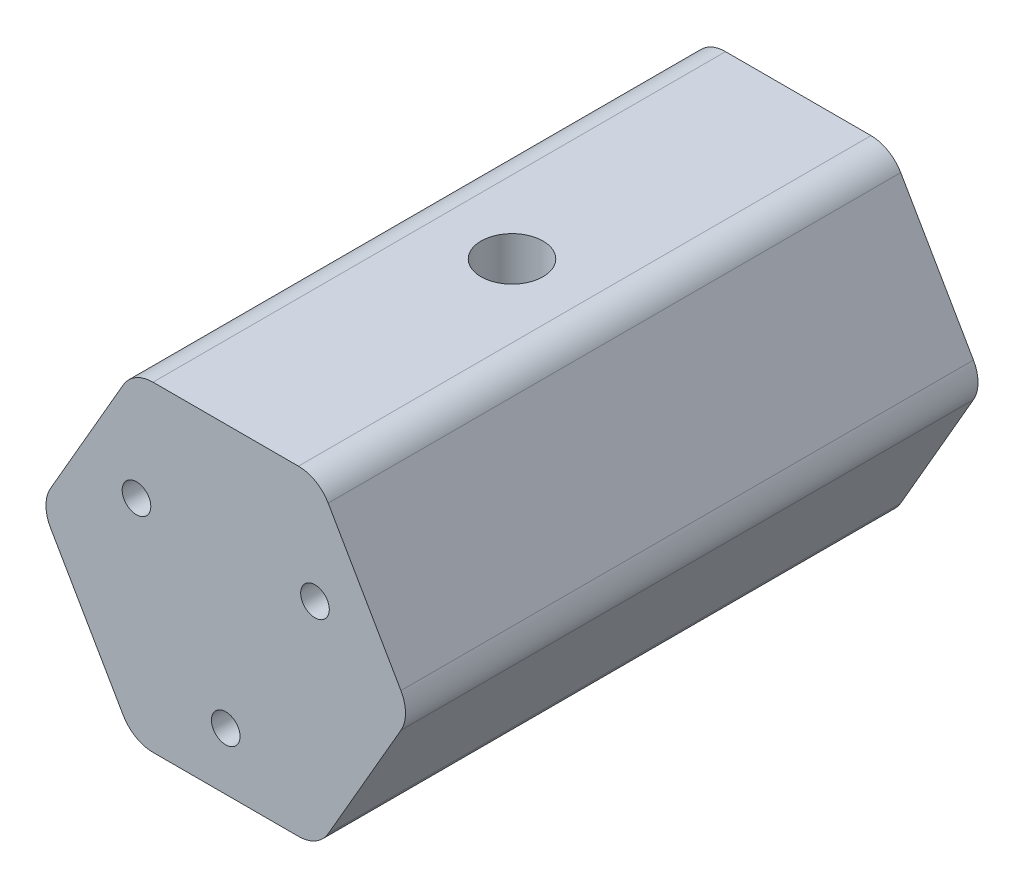
SolidWorks part; units mm, degrees
ref_plane "Front Plane" through (0, 0, 0) normal (0, 0, 1) x (1, 0, 0)
ref_plane "Top Plane" through (0, 0, 0) normal (0, 1, 0) x (1, 0, 0)
ref_plane "Right Plane" through (0, 0, 0) normal (1, 0, 0) x (0, 0, -1)
sketch "Sketch1" plane through (0, 0, 0) normal (0, 0, 1) x (1, 0, 0)
  line L7 (-6.3509, -14) -> (6.3509, -14)
  line L8 (8.9489, -12.5) -> (15.2998, -1.5)
  line L9 (15.2998, 1.5) -> (8.9489, 12.5)
  line L10 (6.3509, 14) -> (-6.3509, 14)
  line L11 (-8.9489, 12.5) -> (-15.2998, 1.5)
  line L12 (-15.2998, -1.5) -> (-8.9489, -12.5)
  circle A0 centre (0, 0) radius 9 construction
  circle A1 centre (-7.7942, 4.5) radius 1.25
  circle A2 centre (7.7942, 4.5) radius 1.25
  circle A3 centre (0, -9) radius 1.25
  circle A4 centre (0, 0) radius 14 construction
  arc A5 (-6.3509, -14) -> (-8.9489, -12.5) centre (-6.3509, -11) cw
  arc A6 (6.3509, -14) -> (8.9489, -12.5) centre (6.3509, -11) ccw
  arc A8 (15.2998, -1.5) -> (15.2998, 1.5) centre (12.7017, 0) ccw
  arc A9 (8.9489, 12.5) -> (6.3509, 14) centre (6.3509, 11) ccw
  arc A10 (-6.3509, 14) -> (-8.9489, 12.5) centre (-6.3509, 11) ccw
  arc A11 (-15.2998, 1.5) -> (-15.2998, -1.5) centre (-12.7017, 0) ccw
  circle A12 centre (0, 0) radius 9 construction
  point P11 (0, 0)
  point P23 (16.1658, 0)
  dimension "D1" = 3
  dimension "D2" = 2.5
  dimension "D3" = 5
  dimension "D4" = 3
extrude "Boss-Extrude1" add sketch "Sketch1" along normal blind 50
sketch "Sketch3" plane through (0, 14, 0) normal (0, 1, 0) x (1, 0, 0)
  line L0 (0, 0) -> (0, -50) construction
  line L1 (6.3509, -50) -> (-6.3509, -50) construction
  point P0 (0, -25)
  point P10 (0, 0)
hole_wizard "1/4-28 Tapped Hole1" positions "Sketch3" profile "Sketch4" tap size "1/4-28" standard "ANSI Inch" end condition through all
cosmetic thread "Hole Thread1" parameters "D2"=6.35
sketch "Sketch4" plane through (0, 14, 25) normal (1, 0, 0) x (0, 0, 1)
  line L0 (0, 0) -> (0, 28)
  line L1 (0, 28) -> (2.7051, 28)
  line L2 (2.7051, 28) -> (2.7051, 0)
  line L5 (2.7051, 0) -> (0, 0)
  line L11 (0, -6.35) -> (0, 107.95) construction
  dimension "Thru Tap Drill Dia." = 5.4102
  dimension "Thru Tap Drill Depth" = 28
equation "\"D1@Boss-Extrude1\"=\"Strut Length@Rocker Bogie Assy.Assembly\""
